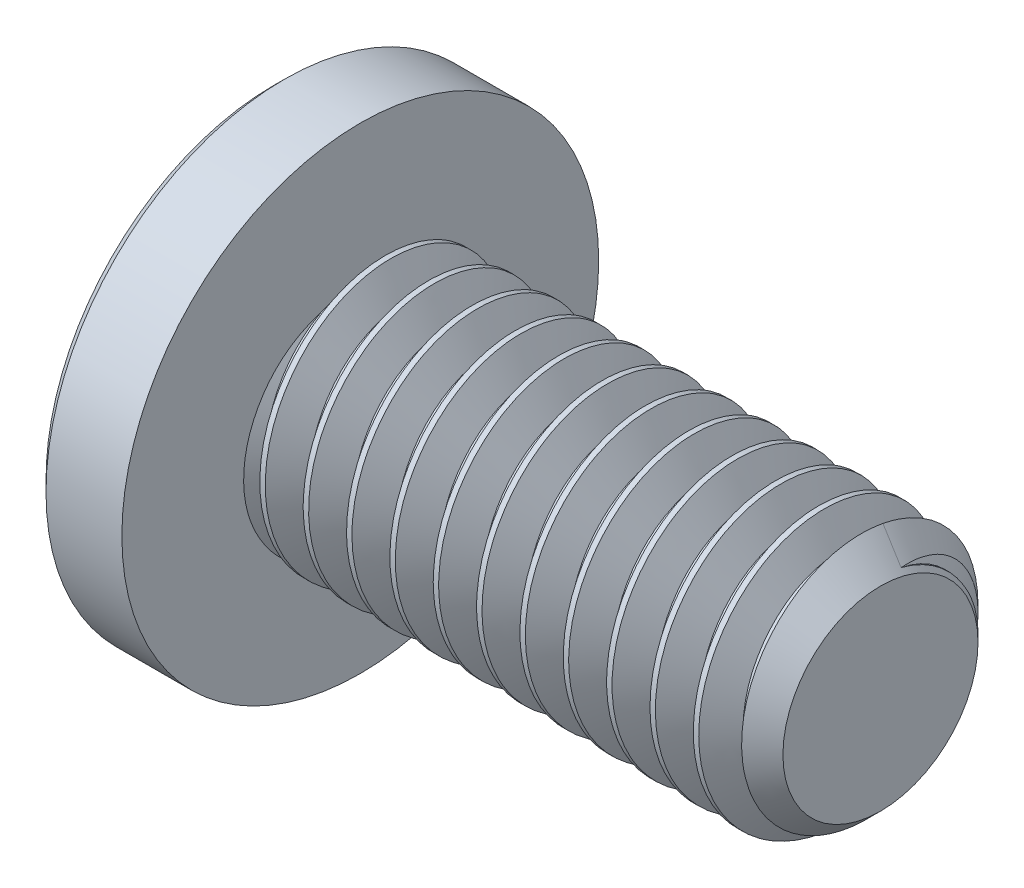
SolidWorks part; units mm, degrees
ref_plane "Front Plane" through (0, 0, 0) normal (0, 0, 1) x (1, 0, 0)
ref_plane "Top Plane" through (0, 0, 0) normal (0, 1, 0) x (1, 0, 0)
ref_plane "Right Plane" through (0, 0, 0) normal (1, 0, 0) x (0, 0, -1)
sketch "Sketch1" plane through (0, 0, 0) normal (0, 0, 1) x (1, 0, 0)
  line L0 (3, 0) -> (-3, 0) construction
  line L1 (3, 1.5) -> (3, -1.5) construction
  line L2 (-3, 2.75) -> (-3, -2.75) construction
  line L3 (-3, 2.75) -> (-3.875, 2.75) construction
  line L4 (-3.875, 2.75) -> (-4, 2.625) construction
  line L5 (-4, 2.625) -> (-4, -2.625) construction
  line L6 (-4, -2.625) -> (-3.875, -2.75) construction
  line L7 (-3.875, -2.75) -> (-3, -2.75) construction
  point P7 (-2.38, 0)
  point P12 (1, -1.5)
  dimension "D1" = 45
  dimension "D2" = 2
  dimension "Dec." = 3
  dimension "Length" = 6
  dimension "Head Dia" = 5.5
  dimension "Head Height" = 1
  dimension "Hex Depth" = 1.62
  dimension "Chamfer" = 0.125
ref_plane "Plane1" through (3, 0, 0) normal (1, 0, 0) x (0, 0, -1)
ref_plane "Plane2" through (-4, 0, 0) normal (1, 0, 0) x (0, 0, -1)
sketch "Sketch2" plane through (3, 0, 0) normal (1, 0, 0) x (0, 0, -1)
  circle A0 centre (0, 0) radius 1.5
extrude "Boss-Extrude1" add sketch "Sketch2" against normal up to vertex (6 mm away) up to point (-3, 0, 0)
sketch "Sketch3" plane through (3, 0, 0) normal (1, 0, 0) x (0, 0, -1)
  circle A0 centre (0, 0) radius 1.5 construction
  circle A1 centre (0, 0) radius 1.5
curve "Helix/Spiral1" pitch 0.5 height 6.5 radius 1.5 centre (3, 0, 0) axis (-1, 0, 0) start towards (0, 1, 0) parameters "Pitch"=0.5
chamfer "Chamfer1" distance 0.375 angle 45 1 edges at (3, 0, -1.5)
sketch "Sketch5" plane through (0, 0, 0) normal (0, 0, 1) x (1, 0, 0)
  line L0 (2.7812, 1.5) -> (3.2188, 1.5)
  line L1 (3.2188, 1.5) -> (3.0312, 1.1752)
  line L2 (3.0312, 1.1752) -> (2.9688, 1.1752)
  line L3 (2.9688, 1.1752) -> (2.7812, 1.5)
  line L4 (3, 1.1752) -> (3, 1.5) construction
  line L5 (2.875, 1.3376) -> (3.125, 1.3376) construction
  dimension "D1" = 60
  dimension "D2" = 0.25
  dimension "D3" = 0.0625
sweep "Cut-Sweep1" cut profiles "Sketch5" path "Helix/Spiral1" align with end faces yes
sketch "Sketch4" plane through (-4, 0, 0) normal (1, 0, 0) x (0, 0, -1)
  line L0 (-2.75, 0.7937) -> (2.75, 0.7937) construction
  line L1 (0, 1.1547) -> (-1, 0.5774)
  line L2 (-1, 0.5774) -> (-1, -0.5774)
  line L3 (-1, -0.5774) -> (0, -1.1547)
  line L4 (0, -1.1547) -> (1, -0.5774)
  line L5 (1, -0.5774) -> (1, 0.5774)
  line L6 (1, 0.5774) -> (0, 1.1547)
  line L7 (0, 0) -> (0, 0.7937) construction
  circle A0 centre (0, 0) radius 1 construction
  dimension "D1" = 5.5
  dimension "Hex Size" = 2
  dimension "D2" = 0.7937
sketch "Sketch6" plane through (0, 0, 0) normal (0, 0, 1) x (1, 0, 0)
  line L0 (-3.875, 2.75) -> (-4, 2.625) construction
  line L1 (-3, 2.75) -> (-3.875, 2.75) construction
  line L2 (-3, 2.75) -> (-3, -2.75) construction
  line L3 (-4, 2.625) -> (-4, -2.625) construction
  line L4 (-3.875, 2.75) -> (-4, 2.625)
  line L5 (-3, 2.75) -> (-3.875, 2.75)
  line L6 (-3, 2.75) -> (-3, 0)
  line L7 (-4, 2.625) -> (-4, 0)
  line L8 (-3, 0) -> (-4, 0) construction
  line L9 (-3, 0) -> (-4, 0)
revolve "Revolve1" add sketch "Sketch6" angle 360 about L8
extrude "Cut-Extrude1" cut sketch "Sketch4" along normal up to vertex (1.62 mm away) up to point (-2.38, 0, 0)
sketch "Sketch8" plane through (-4, 0, 0) normal (-1, 0, 0) x (0, 0, 1)
  circle A1 centre (0, 0) radius 1.1547
extrude "Cut-Extrude2" cut sketch "Sketch8" against normal through all draft 45
equation "\"D3@Helix/Spiral1\" = \"Length@Sketch1\"+\"Pitch@Helix/Spiral1\""
equation "\"D3@Sketch5\" = \"Pitch@Helix/Spiral1\"*.125"
equation "\"D2@Sketch5\" = \"Pitch@Helix/Spiral1\"*.50"
equation "\"D1@Chamfer1\" = \"Pitch@Helix/Spiral1\"*.75"
equation "\"D2@Sketch1\" = \"Pitch@Helix/Spiral1\"*4"
equation "\"D1@Sketch4\" = \"Head Dia@Sketch1\""
equation "\"Chamfer@Sketch1\" = \"Head Height@Sketch1\"/8"
